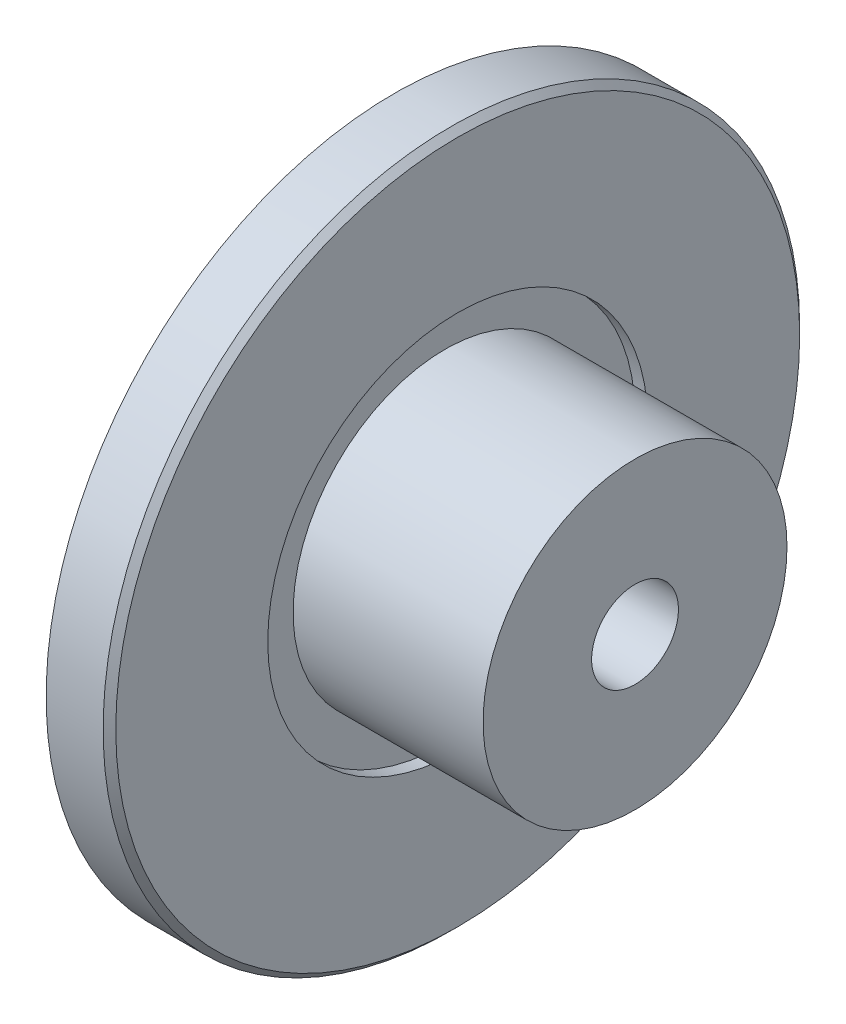
SolidWorks part; units mm, degrees
material "UNOBTANIUM"
ref_plane "Top Plane" through (0, 0, 0) normal (0, 0, 1) x (1, 0, 0)
ref_plane "Right Plane" through (0, 0, 0) normal (0, 1, 0) x (1, 0, 0)
ref_plane "Front Plane" through (0, 0, 0) normal (1, 0, 0) x (0, 0, -1)
ref_axis "x-axis" through (-1.9, 0, 0) along (1, 0, 0)
ref_axis "y-axis" through (0, -23.65, 0) along (0, 1, 0)
ref_axis "z-axis" through (0, 0, 23.65) along (0, 0, -1)
sketch "Sketch1" plane through (0, 0, 0) normal (1, 0, 0) x (0, 0, -1)
  circle A0 centre (0, 0) radius 27.5
  dimension "D1" = 55
extrude "Boss-Extrude1" add sketch "Sketch1" along normal blind 4
sketch "Sketch2" plane through (4, 0, 0) normal (1, 0, 0) x (0, 0, -1)
  circle A0 centre (0, 0) radius 15
  circle A1 centre (0, 0) radius 27.5
  circle A2 centre (0, 0) radius 27.5
  dimension "D2" = 30
  dimension "D1" = 0
extrude "Boss-Extrude2" add sketch "Sketch2" along normal blind 1
sketch "Sketch3" plane through (0, 0, 0) normal (-1, 0, 0) x (0, 0, 1)
  circle A0 centre (0, 0) radius 3.429
  dimension "D1" = 6.858
extrude "Cut-Extrude1" cut sketch "Sketch3" against normal through all both and the other way through all
sketch "Sketch4" plane through (4, 0, 0) normal (1, 0, 0) x (0, 0, -1)
  line L1 (6.9282, -12) -> (13.8564, 0) construction
  line L2 (13.8564, 0) -> (6.9282, 12) construction
  line L3 (6.9282, 12) -> (-6.9282, 12) construction
  line L4 (-6.9282, 12) -> (-13.8564, 0) construction
  line L5 (-13.8564, 0) -> (-6.9282, -12) construction
  line L6 (-6.9282, -12) -> (6.9282, -12) construction
  circle A0 centre (0, 0) radius 12
  circle A1 centre (0, 0) radius 3.429 construction
  circle A2 centre (0, 0) radius 3.429
  dimension "D1" = 24
extrude "Boss-Extrude3" add sketch "Sketch4" along normal blind 15
chamfer "Chamfer1" distance 0.5 angle 45 1 edges at (5, 0, -27.5)
